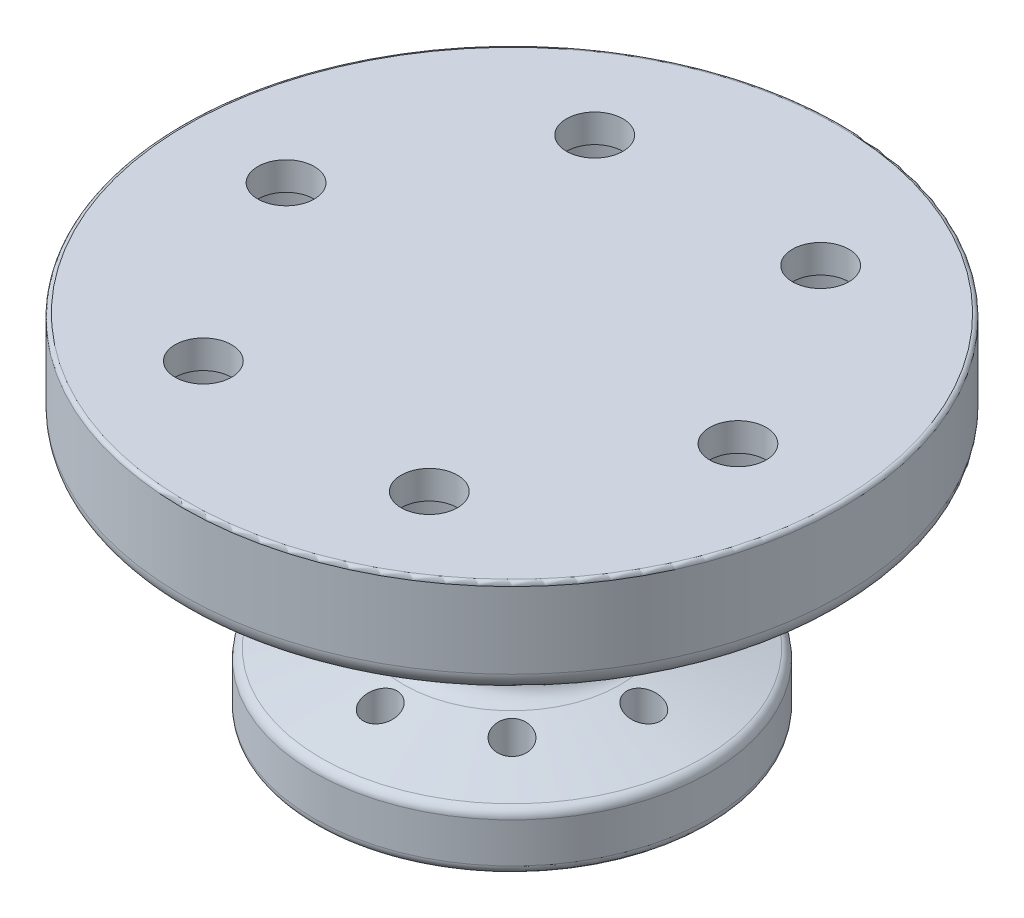
SolidWorks part; units mm, degrees
ref_plane "Front Plane" through (0, 0, 0) normal (0, 0, 1) x (1, 0, 0)
ref_plane "Top Plane" through (0, 0, 0) normal (0, 1, 0) x (1, 0, 0)
ref_plane "Right Plane" through (0, 0, 0) normal (1, 0, 0) x (0, 0, -1)
sketch "Sketch1" plane through (0, 0, 0) normal (0, 0, 1) x (1, 0, 0)
  line L0 (0, 0) -> (17.5, 0)
  line L1 (17.5, 0) -> (17.5, -5)
  line L3 (0, 0) -> (0, -18.5)
  line L4 (5, -8.3494) -> (5, -14.0263)
  line L5 (0, -18.5) -> (10.5, -18.5)
  line L6 (10.5, -18.5) -> (10.5, -15.5)
  line L8 (5, -14.0263) -> (10.5, -15.5)
  line L9 (5, -8.3494) -> (17.5, -5)
  dimension "D1" = 17.5
  dimension "D2" = 5
  dimension "D3" = 18.5
  dimension "D4" = 15
  dimension "D5" = 10.5
  dimension "D6" = 15
  dimension "D7" = 3
  dimension "D8" = 5
revolve "Revolve1" add sketch "Sketch1" angle 360 about L3
sketch "Sketch3" plane through (0, 0, 0) normal (0, 1, 0) x (1, 0, 0)
  line L0 (0, 0) -> (17.5, 0) construction
  circle A0 centre (0, 0) radius 17.5 construction
  circle A1 centre (12, 0) radius 1.5
  circle A2 centre (12, 0) radius 3
  circle A3 centre (6, -10.3923) radius 1.5
  circle A4 centre (6, -10.3923) radius 3
  circle A5 centre (-6, -10.3923) radius 1.5
  circle A6 centre (-6, -10.3923) radius 3
  circle A7 centre (-12, 0) radius 1.5
  circle A8 centre (-12, 0) radius 3
  circle A9 centre (-6, 10.3923) radius 1.5
  circle A10 centre (-6, 10.3923) radius 3
  circle A11 centre (6, 10.3923) radius 1.5
  circle A12 centre (6, 10.3923) radius 3
  point P26 (0, 0)
  dimension "D1" = 12
  dimension "D2" = 3
  dimension "D3" = 6
  dimension "D4" = 6
extrude "Cut-Extrude1" cut sketch "Sketch3" against normal up to next contours A7 | A9 | A11 | L0 A1 | A1 L0 | A3 | A5 region at (12, 0, 0.6366) region at (12, 0, -0.6366) region at (6, 0, 10.3923) region at (-6, 0, 10.3923) region at (-12, 0, 0) region at (-6, 0, -10.3923) region at (6, 0, -10.3923)
extrude "Cut-Extrude2" cut sketch "Sketch3<3>" against normal up to next from offset 1.5 contours A4 A3 | A8 A7 | A10 A9 | A2 L0 A1 | L0 A2 A1 | A6 | A12 region at (12, 0, -1.5671) region at (14.25, 0, 0.0671) region at (3.0849, 0, 10.3923) region at (-14.9151, 0, 0) region at (-8.9151, 0, -10.3923) offset against normal yes
sketch "Sketch3<3>" plane through (0, 0, 0) normal (0, 1, 0) x (1, 0, 0) same geometry as "Sketch3"
fillet "Fillet1" radius 0.2 1 edges at (-17.5, 0, 0)
fillet "Fillet2" radius 1 1 edges at (-17.5, -5, 0)
fillet "Fillet3" radius 1 2 edges at (-5, -8.3494, 0) (-5, -14.0263, 0)
sketch "Sketch4" plane through (0, -18.5, 0) normal (0, -1, 0) x (1, 0, 0)
  line L0 (-0.6679, 0) -> (10.5, 0) construction
  circle A0 centre (0, 0) radius 10.5 construction
  circle A1 centre (7, 0) radius 0.9
  circle A2 centre (0, 0) radius 10.5 construction
  circle A3 centre (0, 0) radius 10.5
  circle A5 centre (4.9497, -4.9497) radius 0.9
  circle A6 centre (0, 0) radius 10.5 construction
  circle A7 centre (0, -7) radius 0.9
  circle A8 centre (0, 0) radius 10.5 construction
  circle A9 centre (-4.9497, -4.9497) radius 0.9
  circle A10 centre (0, 0) radius 10.5 construction
  circle A11 centre (-7, 0) radius 0.9
  circle A12 centre (0, 0) radius 10.5 construction
  circle A13 centre (-4.9497, 4.9497) radius 0.9
  circle A14 centre (0, 0) radius 10.5 construction
  circle A15 centre (0, 7) radius 0.9
  circle A16 centre (0, 0) radius 10.5 construction
  circle A17 centre (4.9497, 4.9497) radius 0.9
  circle A18 centre (0, 0) radius 3.55
  circle A20 centre (0, 0) radius 10.5
  point P35 (0, 0)
  dimension "D1" = 7
  dimension "D2" = 1.8
  dimension "D5" = 7.1
  dimension "D3" = 0
  dimension "D4" = 8
extrude "Cut-Extrude3" cut sketch "Sketch4" against normal up to surface (4.0998 mm away) contours A13 | A15 | A18 | A17 | A1 | A5 | A7 | A9 | A11 region at (7, -18.5, 0) region at (4.9497, -18.5, -4.9497) region at (0, -18.5, -7) region at (-4.9497, -18.5, -4.9497) region at (-7, -18.5, 0) region at (-4.9497, -18.5, 4.9497) region at (0, -18.5, 7) region at (4.9497, -18.5, 4.9497) region at (0, -18.5, 0) up to face at (5.7412, -14.2249, 0)
fillet "Fillet4" radius 0.5 2 edges at (-10.5, -18.5, 0) (-10.5, -15.5, 0)
